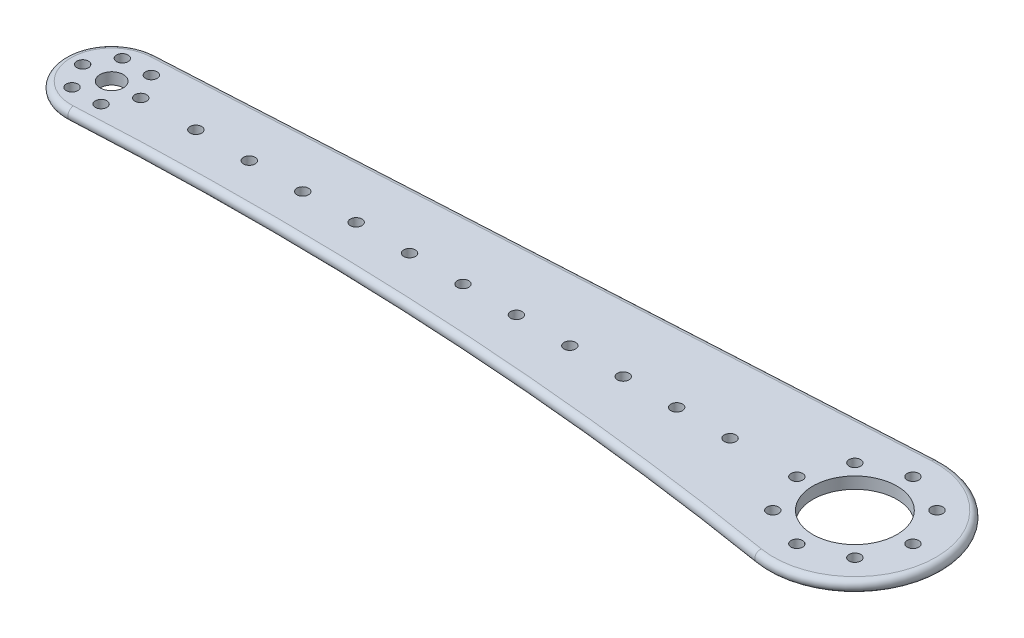
SolidWorks part; units mm, degrees
material "ABS"
ref_plane "Front Plane" through (0, 0, 0) normal (0, 0, 1) x (1, 0, 0)
ref_plane "Top Plane" through (0, 0, 0) normal (0, 1, 0) x (1, 0, 0)
ref_plane "Right Plane" through (0, 0, 0) normal (1, 0, 0) x (0, 0, -1)
ref_axis "Axis1" through (0, 55, 0) along (0, -1, 0)
sketch "Sketch2" plane through (0, 0, 0) normal (0, 1, 0) x (1, 0, 0)
  line L0 (-203.8945, 12.681) -> (-1.3022, 23.7769)
  line L1 (-1.3022, 23.7769) -> (0, 0) construction
  line L2 (-203.8945, 12.681) -> (-202.5055, -12.681) construction
  circle A0 centre (-203.2, 0) radius 12.7 construction
  circle A1 centre (0, 0) radius 23.8125 construction
  circle A2 centre (-0.6077, 11.0959) radius 12.7 construction
  arc A3 (-203.8945, 12.681) -> (-202.5055, -12.681) centre (-203.2, 0) ccw
  arc A4 (-202.5055, -12.681) -> (-3.8759, -23.495) centre (-152.5519, -924.7502) cw
  arc A5 (-1.3022, 23.7769) -> (-3.8759, -23.495) centre (0, 0) cw
  circle A6 centre (0, 0) radius 11.5
  circle A32 centre (0, 0) radius 11.5 construction
  point P14 (0, 0)
  point P16 (0, 0)
  dimension "D1" = 25.4
  dimension "D2" = 47.625
extrude "Boss-Extrude1" add sketch "Sketch2" along normal mid plane 3.175
sketch "Sketch5" plane through (0, 0, 0) normal (0, 1, 0) x (1, 0, 0)
  line L0 (0, 0) -> (0, 15.875) construction
  circle A0 centre (0, 15.875) radius 1.5875
  dimension "D1" = 3.175
  dimension "D2" = 15.875
extrude "Cut-Extrude3" cut sketch "Sketch5" against normal through all both and the other way through all
pattern_circular "CirPattern1" count 8 over 360 about axis through (0, 55, 0) along (0, -1, 0) of "Cut-Extrude3"
sketch "Sketch3" plane through (0, 0, 0) normal (0, 1, 0) x (1, 0, 0)
  line L0 (-34.1312, 0) -> (-23.8125, 0) construction
  line L2 (-190.5, 0) -> (-180.1812, 0) construction
  circle A1 centre (-34.1312, 0) radius 1.5875
  circle A2 centre (-180.1812, 0) radius 1.5875
  circle A3 centre (-165.5762, 0) radius 1.5875
  circle A4 centre (-150.9712, 0) radius 1.5875
  circle A5 centre (-136.3662, 0) radius 1.5875
  circle A6 centre (-121.7612, 0) radius 1.5875
  circle A7 centre (-107.1562, 0) radius 1.5875
  circle A8 centre (-92.5512, 0) radius 1.5875
  circle A9 centre (-77.9462, 0) radius 1.5875
  circle A10 centre (-63.3412, 0) radius 1.5875
  circle A11 centre (-48.7362, 0) radius 1.5875
  arc A12 (-203.8945, 12.681) -> (-202.5055, -12.681) centre (-203.2, 0) ccw construction
  arc A14 (-3.8759, -23.495) -> (-1.3022, 23.7769) centre (0, 0) ccw construction
  point P4 (-22.4367, -0.581)
  point P6 (-23.5533, 0)
  point P7 (0, 0)
  point P9 (-27.3523, 0)
  dimension "D2" = 3.175
  dimension "D1" = 146.05
  dimension "D3" = 11
extrude "Cut-Extrude1" cut sketch "Sketch3" against normal through all both and the other way through all
sketch "Sketch4" plane through (0, 0, 0) normal (0, -1, 0) x (1, 0, 0)
  line L0 (-203.2, 0) -> (-195.2625, 0) construction
  circle A0 centre (-203.2, 0) radius 3.175
  circle A1 centre (-195.2625, 0) radius 1.5875
  dimension "D1" = 6.35
  dimension "D2" = 3.175
  dimension "D3" = 7.9375
extrude "Cut-Extrude2" cut sketch "Sketch4" against normal through all both and the other way through all
pattern_circular "CirPattern2" count 6 over 360 about axis through (-203.2, 1.5875, 0) along (0, -1, 0) of "Cut-Extrude2" reverse direction yes
fillet "Fillet1" 2 edges at (-102.8954, 1.5875, 12.6648) (-102.8954, -1.5875, 12.6648) type full round first side face at (-211.1375, 1.5875, 1.5875) second side face at (-211.1375, -1.5875, 1.5875) middle face at (-103.043, 0, 15.3764)
